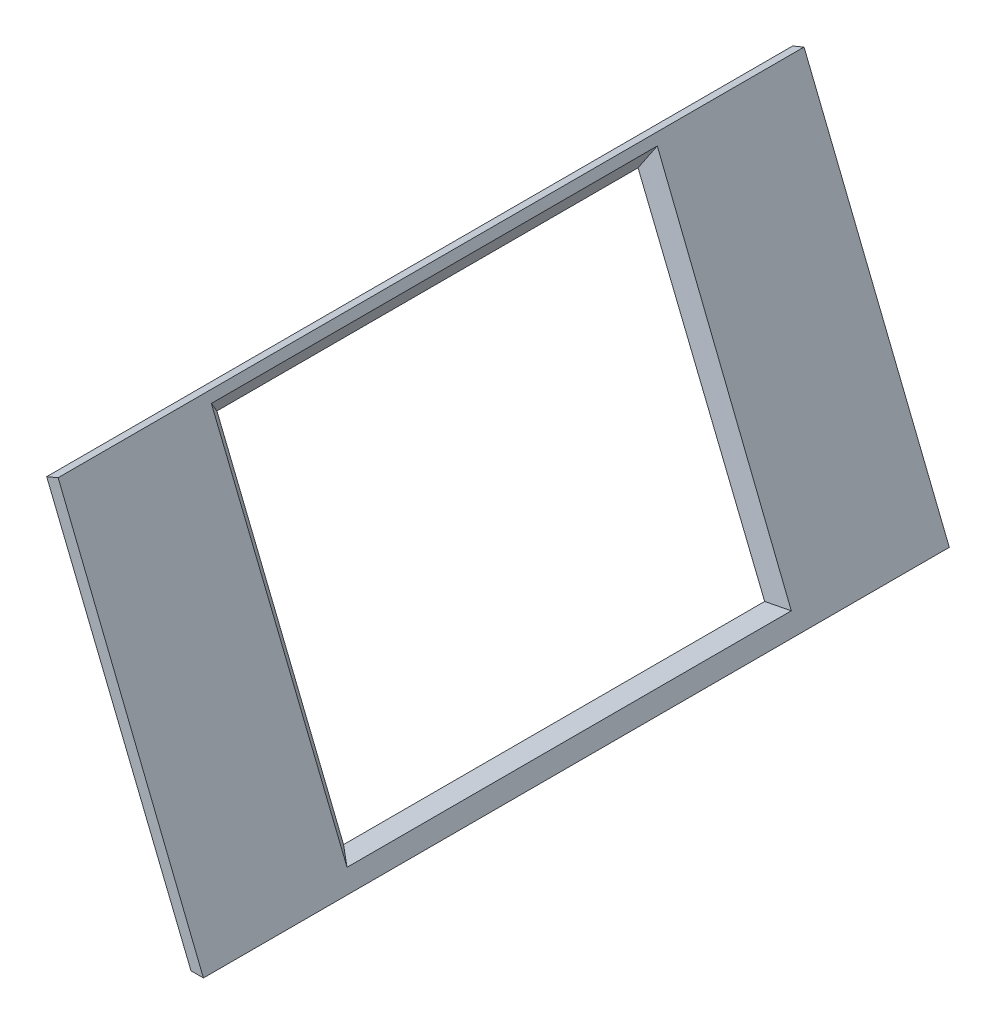
SolidWorks part; units mm, degrees
ref_plane "Plan de face" through (0, 0, 0) normal (0, 0, 1) x (1, 0, 0)
ref_plane "Plan de dessus" through (0, 0, 0) normal (0, 1, 0) x (1, 0, 0)
ref_plane "Plan de droite" through (0, 0, 0) normal (1, 0, 0) x (0, 0, -1)
sketch "Esquisse1" plane through (0, 0, 0) normal (0, 0, 1) x (1, 0, 0)
  line L0 (219.7345, 127.183) -> (103.6557, 413.4004)
  line L1 (103.6557, 413.4004) -> (112.8744, 417.2754)
  line L3 (112.8744, 417.2754) -> (229.7345, 127.183)
  line L4 (229.7345, 127.183) -> (219.7345, 127.183)
  dimension "D1" = 10
extrude "Boss.-Extru.1" add sketch "Esquisse1" along normal blind 600
sketch "Esquisse2" plane through (232.9924, 94.4928, 0) normal (-0.9267, -0.3758, 0) x (0, 0, 1)
  line L1 (130.8597, 326.6879) -> (469.6057, 326.6879)
  line L2 (130.8597, 326.6879) -> (130.8597, 55.6879)
  line L3 (130.8597, 55.6879) -> (469.6057, 55.6879)
  line L4 (469.6057, 326.6879) -> (469.6057, 55.6879)
extrude "Enlèv. mat.-Extru.1" cut sketch "Esquisse2" against normal blind 10 draft 45 draft outward yes
